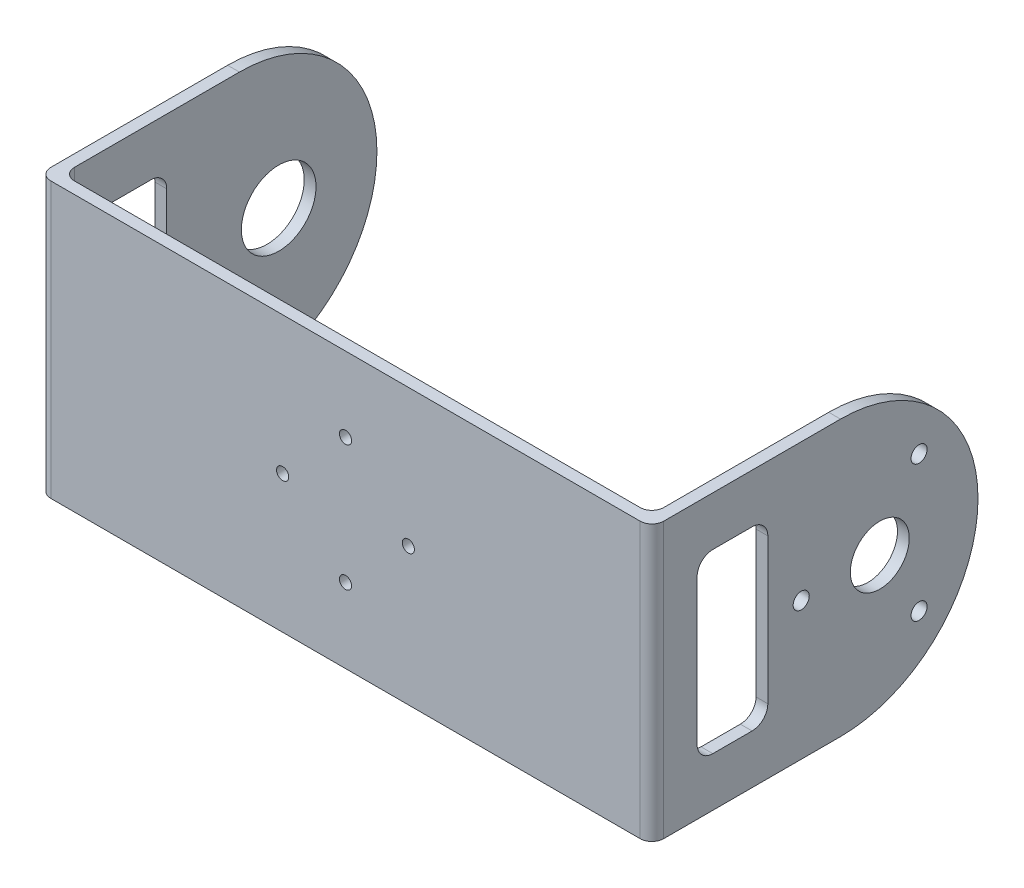
SolidWorks part; units mm, degrees
material "6061 合金"
ref_plane "前视基准面" through (0, 0, 0) normal (0, 0, 1) x (1, 0, 0)
ref_plane "上视基准面" through (0, 0, 0) normal (0, 1, 0) x (1, 0, 0)
ref_plane "右视基准面" through (0, 0, 0) normal (1, 0, 0) x (0, 0, -1)
sketch "草图1" plane through (0, 0, 0) normal (0, 1, 0) x (1, 0, 0)
  line L0 (-75, 0) -> (75, 0)
  line L1 (0, 0) -> (0, -3) construction
  line L2 (-75, 80) -> (-78, 80)
  line L3 (75, 0) -> (75, 80)
  line L4 (-78, 80) -> (-78, -3)
  line L5 (78, -3) -> (-78, -3)
  line L6 (78, 80) -> (78, -3)
  line L7 (75, 80) -> (78, 80)
  line L8 (-75, 0) -> (-75, 80)
extrude "凸台-拉伸1" add sketch "草图1" along normal blind 70
fillet "圆角1" radius 3 4 edges at (75, 35, 0) (-75, 35, 0) (78, 35, 3) (-78, 35, 3)
sketch "草图4" plane through (0, 0, 0) normal (0, 0, -1) x (-1, 0, 0)
  circle A0 centre (0, 35) radius 16 construction
  circle A1 centre (0, 51) radius 1.55
  circle A2 centre (16, 35) radius 1.55
  circle A3 centre (0, 19) radius 1.55
  circle A4 centre (-16, 35) radius 1.55
  point P14 (0, 35)
  dimension "D1" = 32
  dimension "D2" = 3.1
  dimension "D3" = 35
  dimension "D4" = 4
extrude "φ3.1通孔" cut sketch "草图4" against normal blind 70
sketch "草图13" plane through (78, 0, 0) normal (1, 0, 0) x (0, 0, -1)
  line L0 (80, 70) -> (80, 0) construction
  circle A0 centre (55, 35) radius 20 construction
  circle A1 centre (35, 35) radius 2.05
  circle A2 centre (65, 52.3205) radius 2.05
  circle A3 centre (65, 17.6795) radius 2.05
  circle A4 centre (55, 35) radius 7.5
  point P2 (80, 35)
  point P14 (55, 35)
  dimension "D2" = 40
  dimension "D3" = 4.1
  dimension "D5" = 15
  dimension "D1" = 25
  dimension "D4" = 3
extrude "切除-拉伸8" cut sketch "草图13" against normal blind 10
fillet "圆角6" radius 35 4 edges at (-76.5, 70, -80) (-76.5, 0, -80) (76.5, 70, -80) (76.5, 0, -80)
sketch "草图14" plane through (-78, 0, 0) normal (-1, 0, 0) x (0, 0, 1)
  circle A0 centre (-55, 35) radius 9.5
  dimension "D2" = 19
  dimension "D1" = 25
extrude "切除-拉伸9" cut sketch "草图14" against normal blind 10
sketch "草图15" plane through (78, 0, 0) normal (1, 0, 0) x (0, 0, -1)
  line L0 (-3, 0) -> (-3, 70) construction
  line L1 (8.5, 57.5) -> (26.5, 57.5)
  line L2 (8.5, 57.5) -> (8.5, 12.5)
  line L3 (8.5, 12.5) -> (26.5, 12.5)
  line L4 (26.5, 57.5) -> (26.5, 12.5)
  line L5 (8.5, 57.5) -> (26.5, 12.5) construction
  line L6 (8.5, 12.5) -> (26.5, 57.5) construction
  point P0 (17.5, 35)
  dimension "D1" = 20.5
  dimension "D2" = 45
  dimension "D3" = 18
extrude "切除-拉伸11" cut sketch "草图15" against normal through all
fillet "圆角7" radius 4 8 edges at (-76.5, 57.5, -26.5) (-76.5, 12.5, -26.5) (-76.5, 12.5, -8.5) (-76.5, 57.5, -8.5) (76.5, 12.5, -26.5) (76.5, 12.5, -8.5) (76.5, 57.5, -8.5) (76.5, 57.5, -26.5)
